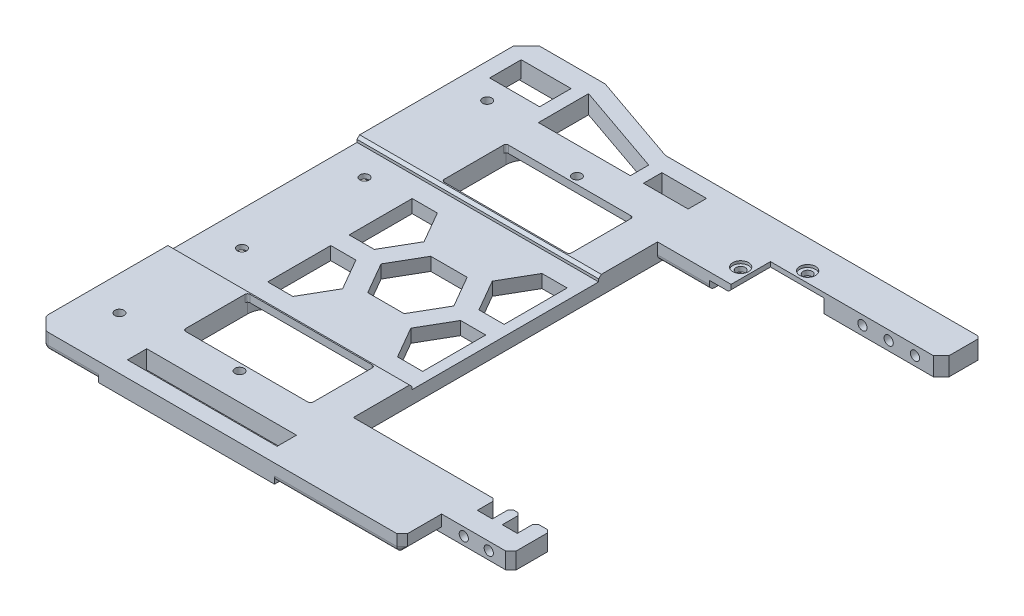
SolidWorks part; units mm, degrees
ref_plane "Front Plane" through (0, 0, 0) normal (0, 0, 1) x (1, 0, 0)
ref_plane "Top Plane" through (0, 0, 0) normal (0, 1, 0) x (1, 0, 0)
ref_plane "Right Plane" through (0, 0, 0) normal (1, 0, 0) x (0, 0, -1)
sketch "Sketch1" plane through (0, 0, 0) normal (0, 1, 0) x (1, 0, 0)
  line L0 (0, -49.205) -> (0, 49.205)
  line L1 (0, 0) -> (215.6, 0)
  line L2 (-50, -76.1325) -> (-50, 92.3676) construction
  line L3 (-25, 41.205) -> (25, 41.205)
  line L4 (-25, 41.205) -> (-25, 57.205)
  line L5 (-25, 57.205) -> (25, 57.205)
  line L6 (25, 41.205) -> (25, 57.205)
  line L7 (-25, 41.205) -> (25, 57.205) construction
  line L8 (-25, 57.205) -> (25, 41.205) construction
  line L9 (-25, -57.205) -> (25, -57.205)
  line L10 (-25, -57.205) -> (-25, -41.205)
  line L11 (-25, -41.205) -> (25, -41.205)
  line L12 (25, -57.205) -> (25, -41.205)
  line L13 (-25, -57.205) -> (25, -41.205) construction
  line L14 (-25, -41.205) -> (25, -57.205) construction
  line L15 (190.6, -8) -> (240.6, -8)
  line L16 (190.6, -8) -> (190.6, 8)
  line L17 (190.6, 8) -> (240.6, 8)
  line L18 (240.6, -8) -> (240.6, 8)
  line L19 (190.6, -8) -> (240.6, 8) construction
  line L20 (190.6, 8) -> (240.6, -8) construction
  line L21 (265.6, 85.2319) -> (265.6, -82.377) construction
  point P4 (0, 0)
  dimension "D1" = 50
  dimension "D2" = 16
  dimension "D3" = 98.41
  dimension "D4" = 215.6
  dimension "D5" = 50
  dimension "D6" = 50
sketch "Sketch2" plane through (0, 0, 0) normal (0, 1, 0) x (1, 0, 0)
  line L1 (10, 87.9) -> (130, 87.9)
  line L3 (37, -87.9) -> (-55, -87.9)
  line L4 (37, -87.9) -> (112, -87.9)
  line L5 (10, 87.9) -> (-25, 100)
  line L6 (-25, 100) -> (-55, 100)
  line L7 (-55, 100) -> (-55, -87.9)
  line L8 (37, -87.9) -> (37, 57.9) construction
  line L9 (37, 57.9) -> (130, 57.9)
  line L10 (130, 57.9) -> (130, 87.9)
  line L11 (10, 87.9) -> (10, -87.9) construction
  line L12 (0, 0) -> (215.6, 0) construction
  line L14 (0, -49.205) -> (0, 49.205) construction
  line L15 (112, -87.9) -> (112, -57.9)
  line L16 (112, -57.9) -> (37, -57.9)
  line L17 (37, -57.9) -> (37, 57.9)
  point P8 (10, 0)
  dimension "D1" = 100
  dimension "D2" = 92
  dimension "D3" = 30
  dimension "D4" = 87.9
  dimension "D5" = 30
  dimension "D6" = 55
  dimension "D7" = 130
  dimension "D8" = 65
  dimension "D9" = 30
  dimension "D10" = 75
extrude "Boss-Extrude1" add sketch "Sketch2" along normal blind 7
sketch "Sketch3" plane through (0, 0, 0) normal (0, -1, 0) x (1, 0, 0)
  line L0 (-25, -100) -> (-55, -100) construction
  line L1 (-55, 87.9) -> (-30, 87.9)
  line L2 (-55, 87.9) -> (-55, -92)
  line L3 (-55, -92) -> (-30, -92)
  line L4 (-30, 87.9) -> (-30, -92)
  dimension "D1" = 8
  dimension "D2" = 30
extrude "Cut-Extrude1" cut sketch "Sketch3" against normal blind 0.75
sketch "Sketch4" plane through (0, 0, 0) normal (0, -1, 0) x (1, 0, 0)
  line L0 (-25, 57.205) -> (25, 41.205) construction
  line L1 (24.25, -68.555) -> (-24.25, -68.555)
  line L2 (24.25, -68.555) -> (24.25, -29.855)
  line L3 (24.25, -29.855) -> (-24.25, -29.855)
  line L4 (-24.25, -68.555) -> (-24.25, -29.855)
  line L5 (24.25, -68.555) -> (-24.25, -29.855) construction
  line L6 (24.25, -29.855) -> (-24.25, -68.555) construction
  line L7 (24.25, 68.555) -> (-24.25, 68.555)
  line L8 (24.25, 68.555) -> (24.25, 29.855)
  line L9 (24.25, 29.855) -> (-24.25, 29.855)
  line L10 (-24.25, 68.555) -> (-24.25, 29.855)
  line L11 (24.25, 68.555) -> (-24.25, 29.855) construction
  line L12 (24.25, 29.855) -> (-24.25, 68.555) construction
  point P0 (0, -49.205)
  point P5 (0, 49.205)
  dimension "D1" = 48.5
  dimension "D2" = 38.7
extrude "Cut-Extrude2" cut sketch "Sketch4" against normal blind 4.2
sketch "Sketch5" plane through (0, 0, 0) normal (0, -1, 0) x (1, 0, 0)
  line L0 (-25, 57.205) -> (25, 41.205) construction
  line L1 (24.25, -36.955) -> (-24.25, -36.955)
  line L2 (24.25, -36.955) -> (24.25, -61.455)
  line L3 (24.25, -61.455) -> (-24.25, -61.455)
  line L4 (-24.25, -36.955) -> (-24.25, -61.455)
  line L5 (24.25, -36.955) -> (-24.25, -61.455) construction
  line L6 (24.25, -61.455) -> (-24.25, -36.955) construction
  line L7 (24.25, 61.455) -> (-24.25, 61.455)
  line L8 (24.25, 61.455) -> (24.25, 36.955)
  line L9 (24.25, 36.955) -> (-24.25, 36.955)
  line L10 (-24.25, 61.455) -> (-24.25, 36.955)
  line L11 (24.25, 61.455) -> (-24.25, 36.955) construction
  line L12 (24.25, 36.955) -> (-24.25, 61.455) construction
  line L13 (-24.25, 68.555) -> (-24.25, 29.855) construction
  line L14 (-24.25, -29.855) -> (-24.25, -68.555) construction
  point P0 (0, -49.205)
  point P5 (0, 49.205)
  dimension "D1" = 24.5
extrude "Cut-Extrude3" cut sketch "Sketch5" against normal through all
fillet "Fillet1" radius 7 8 edges at (-24.25, 2.1, 29.855) (-24.25, 2.1, 68.555) (24.25, 2.1, 29.855) (24.25, 2.1, 68.555) (24.25, 2.1, -29.855) (-24.25, 2.1, -29.855) (-24.25, 2.1, -68.555) (24.25, 2.1, -68.555)
fillet "Fillet2" radius 1 8 edges at (-24.25, 5.6, -36.955) (-24.25, 5.6, -61.455) (24.25, 5.6, -61.455) (24.25, 5.6, -36.955) (24.25, 5.6, 36.955) (24.25, 5.6, 61.455) (-24.25, 5.6, 36.955) (-24.25, 5.6, 61.455)
sketch "Sketch7" plane through (0, 0, 0) normal (0, -1, 0) x (1, 0, 0)
  line L1 (130, -57.9) -> (65, -57.9)
  line L2 (130, -57.9) -> (130, -72.9)
  line L3 (130, -72.9) -> (65, -72.9)
  line L4 (65, -57.9) -> (65, -72.9)
  line L5 (0, 0) -> (215.6, 0) construction
  line L6 (0, 49.205) -> (0, -49.205) construction
  dimension "D1" = 72.9
  dimension "D2" = 65
extrude "Cut-Extrude4" cut sketch "Sketch7" against normal through all
sketch "Sketch8" plane through (0, 7, 0) normal (0, 1, 0) x (1, 0, 0)
  line L0 (-55, 100) -> (-55, -87.9) construction
  line L1 (-55, -35.5) -> (37, -35.5)
  line L2 (-55, -35.5) -> (-55, 35.5)
  line L3 (-55, 35.5) -> (37, 35.5)
  line L4 (37, -35.5) -> (37, 35.5)
  line L6 (0, 0) -> (215.6, 0) construction
  line L7 (37, -57.9) -> (37, 57.9) construction
  point P8 (37, 0)
  dimension "D1" = 71
extrude "Cut-Extrude5" cut sketch "Sketch8" against normal blind 2
chamfer "Chamfer1" distance 1 angle 45 2 edges at (-9, 7, 35.5) (-9, 7, -35.5)
sketch "Sketch9" plane through (0, 0, 0) normal (0, -1, 0) x (1, 0, 0)
  line L0 (85.3, -57.9) -> (85.3, -80.9)
  line L2 (85.3, -80.9) -> (56.7, -80.9)
  line L4 (56.7, -80.9) -> (56.7, -57.9)
  line L6 (56.7, -57.9) -> (85.3, -57.9)
  line L8 (37, -57.9) -> (65, -57.9) construction
  line L9 (65, -57.9) -> (65, -72.9) construction
  line L10 (65, -72.9) -> (130, -72.9) construction
  dimension "D2" = 8.3
  dimension "D3" = 8
  dimension "D4" = 20.3
extrude "Cut-Extrude6" cut sketch "Sketch9" against normal blind 4.2
fillet "Fillet3" radius 4 1 edges at (56.7, 2.1, -80.9)
sketch "Sketch12" plane through (0, 0, 0) normal (0, -1, 0) x (1, 0, 0)
  line L0 (0, 0) -> (215.6, 0) construction
  line L1 (-10.3564, 0) -> (-3.4282, -12)
  line L2 (-3.4282, -12) -> (10.4282, -12)
  line L3 (10.4282, -12) -> (17.3564, 0)
  line L4 (17.3564, 0) -> (10.4282, 12)
  line L5 (10.4282, 12) -> (-3.4282, 12)
  line L6 (-3.4282, 12) -> (-10.3564, 0)
  line L7 (33, -27.5) -> (33, -3.5)
  line L8 (16.4904, -15.5) -> (23.4186, -27.5)
  line L9 (23.4186, -27.5) -> (33, -27.5)
  line L12 (33, -3.5) -> (23.4186, -3.5)
  line L13 (23.4186, -3.5) -> (16.4904, -15.5)
  line L14 (42.4333, -18.5655) -> (48.3862, -8.2549) [skipped]
  line L15 (37.1681, -3.3148) -> (30.9097, 7.5249) [skipped]
  line L16 (33, 3.5) -> (33, 27.5)
  line L17 (16.4904, 15.5) -> (23.4186, 3.5)
  line L18 (23.4186, 3.5) -> (33, 3.5)
  line L19 (33, 27.5) -> (23.4186, 27.5)
  line L20 (23.4186, 27.5) -> (16.4904, 15.5)
  line L21 (30.3468, -15.5) -> (30.3468, 15.5) construction
  line L22 (-26, -27.5) -> (-26, -3.5)
  line L24 (-26, -27.5) -> (-16.4186, -27.5)
  line L25 (-16.4186, -27.5) -> (-9.4904, -15.5)
  line L26 (-9.4904, -15.5) -> (-16.4186, -3.5)
  line L27 (-16.4186, -3.5) -> (-26, -3.5)
  line L30 (-26, 3.5) -> (-16.4186, 3.5)
  line L31 (-16.4186, 3.5) -> (-9.4904, 15.5)
  line L32 (-9.4904, 15.5) -> (-16.4186, 27.5)
  line L33 (-16.4186, 27.5) -> (-26, 27.5)
  line L35 (-38.0283, -14.0709) -> (-31.1001, -26.0709) [skipped]
  line L36 (-31.1001, -4.9291) -> (-38.0283, -16.9291) [skipped]
  line L37 (-38.0283, 16.9291) -> (-31.1001, 4.9291) [skipped]
  line L38 (-31.1001, 26.0709) -> (-38.0283, 14.0709) [skipped]
  line L39 (-26, 3.5) -> (-26, 27.5)
  line L41 (-30, -92) -> (-30, 87.9) construction
  line L42 (37, 35.5) -> (37, -35.5) construction
  circle A0 centre (3.5, 0) radius 12 construction
  circle A1 centre (30.3468, -15.5) radius 12 construction
  circle A2 centre (30.3468, 15.5) radius 12 construction
  circle A3 centre (-23.3468, -15.5) radius 12 construction
  circle A4 centre (-23.3468, 15.5) radius 12 construction
  dimension "D1" = 24
  dimension "D2" = 24
  dimension "D3" = 24
  dimension "D8" = 24
  dimension "D9" = 24
  dimension "D4" = 120
  dimension "D5" = 7
  dimension "D6" = 7
  dimension "D7" = 7
  dimension "D10" = 7
  dimension "D11" = 7
  dimension "D12" = 7
  dimension "D13" = 33.5
  dimension "D14" = 4
  dimension "D15" = 4
extrude "Cut-Extrude8" cut sketch "Sketch12" against normal blind 10
chamfer "Chamfer2" distance 3 angle 45 1 edges at (130, 3.5, -72.9)
sketch "Sketch13" plane through (0, 7, 0) normal (0, 1, 0) x (1, 0, 0)
  line L0 (0, 0) -> (215.6, 0) construction
  line L1 (112, -87.9) -> (85.6, -87.9)
  line L2 (112, -87.9) -> (112, -72.9)
  line L3 (112, -72.9) -> (85.6, -72.9)
  line L4 (85.6, -87.9) -> (85.6, -72.9)
  dimension "D1" = 72.9
  dimension "D2" = 26.4
extrude "Cut-Extrude9" cut sketch "Sketch13" against normal through all
sketch "Sketch14" plane through (0, 0, 0) normal (0, -1, 0) x (1, 0, 0)
  line L0 (-30, 87.9) -> (85.6, 87.9) construction
  line L1 (37, -72.9) -> (127, -72.9)
  line L2 (37, -72.9) -> (37, 87.9)
  line L3 (37, 87.9) -> (127, 87.9)
  line L4 (127, -72.9) -> (127, 87.9)
  line L6 (37, 57.9) -> (37, -57.9) construction
extrude "Cut-Extrude10" cut sketch "Sketch14" against normal blind 0.75
sketch "Sketch15" plane through (0, 0, -87.9) normal (0, 0, -1) x (-1, 0, 0)
  line L0 (-130, 3.5) -> (-90, 3.5) construction
  line L1 (-130, 7) -> (-130, 0) construction
  line L2 (-130, 0) -> (-10, 0) construction
  line L4 (-121.75, 3.5) -> (-121.75, 0) construction
  line L5 (-121.75, 0) -> (-118.25, 0) construction
  line L6 (-118.25, 3.5) -> (-118.25, 0) construction
  line L7 (-111.75, 3.5) -> (-111.75, 0) construction
  line L8 (-111.75, 0) -> (-108.25, 0) construction
  line L9 (-108.25, 3.5) -> (-108.25, 0) construction
  line L12 (-101.75, 3.5) -> (-101.75, 0) construction
  line L13 (-101.75, 0) -> (-98.25, 0) construction
  line L14 (-98.25, 3.5) -> (-98.25, 0) construction
  arc A0 (-121.75, 3.5) -> (-118.25, 3.5) centre (-120, 3.5) cw
  arc A1 (-111.75, 3.5) -> (-108.25, 3.5) centre (-110, 3.5) cw
  arc A2 (-101.75, 3.5) -> (-98.25, 3.5) centre (-100, 3.5) cw
  arc A3 (-121.75, 3.5) -> (-118.25, 3.5) centre (-120, 3.5) ccw
  arc A4 (-111.75, 3.5) -> (-108.25, 3.5) centre (-110, 3.5) ccw
  arc A5 (-101.75, 3.5) -> (-98.25, 3.5) centre (-100, 3.5) ccw
  point P6 (0, 0)
  dimension "D1" = 1.75
  dimension "D2" = 1.75
  dimension "D3" = 1.75
  dimension "D4" = 40
  dimension "D5" = 10
  dimension "D6" = 10
extrude "Cut-Extrude11" cut sketch "Sketch15" against normal up to next
sketch "Sketch16" plane through (0, -80.9, -87.9) normal (0, 0, 1) x (1, 0, 0)
  circle A0 centre (100, 84.4) radius 2.9
  circle A1 centre (110, 84.4) radius 2.9
  circle A2 centre (120, 84.4) radius 2.9
  dimension "D1" = 5.8
  dimension "D2" = 5.8
  dimension "D3" = 5.8
extrude "Cut-Extrude12" cut sketch "Sketch16" along normal blind 6
sketch "Sketch17" plane through (0, 0, 72.9) normal (0, 0, 1) x (1, 0, 0)
  line L0 (85.6, 3.875) -> (112, 3.875) construction
  line L1 (85.6, 0.75) -> (85.6, 7) construction
  line L2 (112, 0.75) -> (112, 7) construction
  line L3 (85.6, 0.75) -> (112, 0.75) construction
  line L5 (92.3, 3.875) -> (92.3, 0.75) construction
  line L6 (92.3, 0.75) -> (95.8, 0.75) construction
  line L7 (95.8, 3.875) -> (95.8, 0.75) construction
  line L8 (94.05, 3.875) -> (103.55, 3.875) construction
  line L10 (101.8, 3.875) -> (101.8, 0.75) construction
  line L11 (101.8, 0.75) -> (105.3, 0.75) construction
  line L12 (105.3, 3.875) -> (105.3, 0.75) construction
  arc A0 (92.3, 3.875) -> (95.8, 3.875) centre (94.05, 3.875) cw
  arc A1 (101.8, 3.875) -> (105.3, 3.875) centre (103.55, 3.875) cw
  arc A2 (92.3, 3.875) -> (95.8, 3.875) centre (94.05, 3.875) ccw
  arc A3 (101.8, 3.875) -> (105.3, 3.875) centre (103.55, 3.875) ccw
  point P6 (105.3, 3.875)
  point P19 (0, 0)
  point P21 (98.8, 3.875)
  dimension "D1" = 1.75
  dimension "D2" = 9.5
extrude "Cut-Extrude13" cut sketch "Sketch17" against normal up to next
sketch "Sketch18" plane through (0, 7, 0) normal (0, 1, 0) x (1, 0, 0)
  line L0 (112, -57.9) -> (37, -57.9) construction
  line L1 (106.4, -57.9) -> (100.7, -57.9)
  line L2 (106.4, -57.9) -> (106.4, -64.9)
  line L3 (106.4, -64.9) -> (100.7, -64.9)
  line L4 (100.7, -57.9) -> (100.7, -64.9)
  line L5 (95.8, -57.9) -> (92.3, -57.9) construction
  line L6 (96.9, -57.9) -> (91.2, -57.9)
  line L7 (96.9, -57.9) -> (96.9, -64.9)
  line L8 (96.9, -64.9) -> (91.2, -64.9)
  line L9 (91.2, -57.9) -> (91.2, -64.9)
  line L10 (105.3, -57.9) -> (101.8, -57.9) construction
  point P12 (94.05, -57.9)
  point P15 (103.55, -57.9)
  dimension "D1" = 5.7
  dimension "D2" = 7
extrude "Cut-Extrude14" cut sketch "Sketch18" against normal through all
chamfer "Chamfer3" distance 1 angle 45 2 edges at (75.15, 4.2, -72.9) (65, 4.2, -65.4)
sketch "Sketch19" plane through (0, 4.2, 0) normal (0, -1, 0) x (1, 0, 0)
  line L0 (75.15, -72.9) -> (75.15, -65.4) construction
  line L1 (65, -65.4) -> (56.7, -65.4) construction
  line L2 (75.15, -65.4) -> (65, -65.4) construction
  line L4 (56.7, -57.9) -> (56.7, -76.9) construction
  line L5 (75.15, -72.9) -> (75.15, -80.9) construction
  line L6 (65, -72.9) -> (85.3, -72.9) construction
  line L7 (60.7, -80.9) -> (85.3, -80.9) construction
  line L8 (65, -57.9) -> (65, -72.9) construction
  circle A0 centre (61.15, -65.4) radius 1.75
  circle A1 centre (75.15, -76.9) radius 1.75
  dimension "D1" = 3.5
  dimension "D2" = 3.5
  dimension "D3" = 11.5
  dimension "D4" = 14
extrude "Cut-Extrude15" cut sketch "Sketch19" against normal through all
fillet "Fillet4" radius 2 4 edges at (46.85, 0.75, -57.9) (61.3, 0.75, 87.9) (-42.5, 0.75, 87.9) (-55, 0.75, -2.05)
sketch "Sketch20" plane through (0, 7, 0) normal (0, 1, 0) x (1, 0, 0)
  circle A0 centre (61.15, 65.4) radius 3
  circle A1 centre (75.15, 76.9) radius 3
  dimension "D1" = 6
  dimension "D2" = 6
extrude "Cut-Extrude16" cut sketch "Sketch20" against normal blind 1
chamfer "Chamfer5" distance 1 angle 45 5 edges at (112, 3.875, 57.9) (106.4, 3.875, 57.9) (100.7, 3.875, 57.9) (96.9, 3.875, 57.9) (91.2, 3.875, 57.9)
chamfer "Chamfer6" distance 2 angle 45 4 edges at (85.6, 4.875, 87.9) (112, 3.875, 72.9) (85.6, 0.75, 79.4) (85.6, 1.3358, 87.3142)
sketch "Sketch21" plane through (0, 0, 0) normal (0, -1, 0) x (1, 0, 0)
  line L0 (-25, -93.6516) -> (10, -81.5516)
  line L1 (10, -81.5516) -> (10, -74.555)
  line L2 (10, -74.555) -> (-25, -74.555)
  line L3 (-25, -74.555) -> (-25, -93.6516)
  line L4 (10, -87.9) -> (-25, -100) construction
  line L5 (-17.25, -68.555) -> (17.25, -68.555) construction
  line L6 (-30, -92) -> (-30, 85.9) construction
  line L7 (-30, -92) -> (-30, 87.9) construction
  line L8 (32, 74.555) -> (-25, 74.555)
  line L9 (32, 74.555) -> (32, 81.9)
  line L10 (32, 81.9) -> (-25, 81.9)
  line L11 (-25, 74.555) -> (-25, 81.9)
  line L12 (-30, 87.9) -> (37, 87.9) construction
  line L13 (17.25, 68.555) -> (-17.25, 68.555) construction
  line L14 (37, 87.9) -> (37, -72.9) construction
  line L15 (32, -74.555) -> (32, 74.555) construction
  line L16 (15, -74.555) -> (32, -74.555)
  line L17 (15, -74.555) -> (15, -81.5516)
  line L18 (15, -81.5516) -> (32, -81.5516)
  line L19 (32, -74.555) -> (32, -81.5516)
  line L21 (10, -81.5516) -> (15, -81.5516) construction
  line L22 (10, -74.555) -> (15, -74.555) construction
  dimension "D1" = 6
  dimension "D2" = 6
  dimension "D3" = 5
  dimension "D4" = 5
  dimension "D5" = 6
  dimension "D6" = 6
  dimension "D7" = 5
  dimension "D8" = 5
extrude "Cut-Extrude17" cut sketch "Sketch21" against normal through all
sketch "Sketch23" plane through (0, 0.75, 0) normal (0, -1, 0) x (1, 0, 0)
  line L0 (-42, -92) -> (-42, 87.9) construction
  line L1 (-53, -92) -> (-30, -92) construction
  line L2 (-30, 87.9) -> (-55, 87.9) construction
  line L3 (-42, 67.95) -> (-42, -72.05) construction
  line L4 (-38.8246, -72.05) -> (-40.4123, -69.3)
  line L5 (-40.4123, -69.3) -> (-43.5877, -69.3)
  line L6 (-43.5877, -69.3) -> (-45.1754, -72.05) construction
  line L7 (-45.1754, -72.05) -> (-43.5877, -74.8) construction
  line L8 (-43.5877, -74.8) -> (-40.4123, -74.8)
  line L9 (-40.4123, -74.8) -> (-38.8246, -72.05)
  line L10 (-55, 87.9) -> (-55, -92) construction
  line L11 (-38.8246, 67.95) -> (-40.4123, 70.7)
  line L12 (-40.4123, 70.7) -> (-43.5877, 70.7)
  line L13 (-43.5877, 70.7) -> (-45.1754, 67.95) construction
  line L14 (-45.1754, 67.95) -> (-43.5877, 65.2) construction
  line L15 (-43.5877, 65.2) -> (-40.4123, 65.2)
  line L16 (-40.4123, 65.2) -> (-38.8246, 67.95)
  line L17 (-38.8246, -25.3833) -> (-40.4123, -22.6333)
  line L18 (-40.4123, -22.6333) -> (-43.5877, -22.6333)
  line L19 (-43.5877, -22.6333) -> (-45.1754, -25.3833) construction
  line L20 (-45.1754, -25.3833) -> (-43.5877, -28.1333) construction
  line L21 (-43.5877, -28.1333) -> (-40.4123, -28.1333)
  line L22 (-40.4123, -28.1333) -> (-38.8246, -25.3833)
  line L23 (-38.8246, 21.2833) -> (-40.4123, 24.0333)
  line L24 (-40.4123, 24.0333) -> (-43.5877, 24.0333)
  line L25 (-43.5877, 24.0333) -> (-45.1754, 21.2833) construction
  line L26 (-45.1754, 21.2833) -> (-43.5877, 18.5333) construction
  line L27 (-43.5877, 18.5333) -> (-40.4123, 18.5333)
  line L28 (-40.4123, 18.5333) -> (-38.8246, 21.2833)
  line L30 (-43.5877, 70.7) -> (-55, 70.7)
  line L32 (-43.5877, 65.2) -> (-55, 65.2)
  line L33 (-55, 70.7) -> (-55, 65.2)
  line L34 (-43.5877, 18.5333) -> (-55, 18.5333)
  line L36 (-43.5877, 24.0333) -> (-55, 24.0333)
  line L37 (-55, 18.5333) -> (-55, 24.0333)
  line L38 (-43.5877, -22.6333) -> (-55, -22.6333)
  line L40 (-43.5877, -28.1333) -> (-55, -28.1333)
  line L41 (-55, -22.6333) -> (-55, -28.1333)
  line L42 (-43.5877, -69.3) -> (-55, -69.3)
  line L44 (-43.5877, -74.8) -> (-55, -74.8)
  line L45 (-55, -69.3) -> (-55, -74.8)
  circle A0 centre (-42, -72.05) radius 2.75 construction
  circle A1 centre (-42, 67.95) radius 2.75 construction
  circle A2 centre (-42, -25.3833) radius 2.75 construction
  circle A3 centre (-42, 21.2833) radius 2.75 construction
  point P18 (-42, -2.05)
  dimension "D1" = 5.5
  dimension "D2" = 140
  dimension "D3" = 46.6667
  dimension "D4" = 46.6667
  dimension "D5" = 13
extrude "Cut-Extrude18" cut sketch "Sketch23" against normal blind 2.5
chamfer "Chamfer7" distance 1 angle 45 32 edges at (-46.7061, 0.75, 70.7) (-39.6184, 0.75, 69.325) (-46.7061, 0.75, 65.2) (-39.6184, 0.75, 66.575) (-46.7061, 0.75, 24.0333) (-39.6184, 0.75, 22.6583) (-46.7061, 0.75, 18.5333) (-39.6184, 0.75, 19.9083) (-46.7061, 0.75, -22.6333) (-39.6184, 0.75, -24.0083) (-39.6184, 0.75, -26.7583) (-46.7061, 0.75, -28.1333) (-46.7061, 0.75, -69.3) (-46.7061, 0.75, -74.8) (-39.6184, 0.75, -73.425) (-39.6184, 0.75, -70.675) (-55, 3, 70.7) (-55, 3, 65.2) (-54.4142, 1.3358, 70.7) (-54.4142, 1.3358, 65.2) (-55, 3, 24.0333) (-55, 3, 18.5333) (-54.4142, 1.3358, 24.0333) (-54.4142, 1.3358, 18.5333) (-55, 3, -22.6333) (-55, 3, -28.1333) (-54.4142, 1.3358, -22.6333) (-54.4142, 1.3358, -28.1333) (-55, 3, -69.3) (-55, 3, -74.8) (-54.4142, 1.3358, -69.3) (-54.4142, 1.3358, -74.8)
sketch "Sketch24" plane through (0, 0.75, 0) normal (0, -1, 0) x (1, 0, 0)
  circle A0 centre (-42, -72.05) radius 1.75
  circle A1 centre (-42, -25.3833) radius 1.75
  circle A2 centre (-42, 21.2833) radius 1.75
  circle A3 centre (-42, 67.95) radius 1.75
  dimension "D1" = 3.5
extrude "Cut-Extrude19" cut sketch "Sketch24" against normal through all
chamfer "Chamfer8" distance 1 angle 45 1 edges at (130, 3.5, -87.9)
sketch "Sketch25" plane through (0, 0, 0) normal (0, -1, 0) x (1, 0, 0)
  line L0 (-55, -75.8) -> (-55, -92) construction
  line L1 (-30, -92) -> (-49, -92)
  line L2 (-30, -92) -> (-30, -80)
  line L3 (-30, -80) -> (-49, -80)
  line L4 (-49, -92) -> (-49, -80)
  dimension "D1" = 12
  dimension "D2" = 6
extrude "Cut-Extrude20" cut sketch "Sketch25" against normal through all
chamfer "Chamfer9" distance 5 angle 45 2 edges at (-55, 3.5, -100) (-55, 4.875, 87.9)
sketch "Sketch26" plane through (0, 4.2, 0) normal (0, -1, 0) x (1, 0, 0)
  line L0 (0, -68.555) -> (0, -61.455) construction
  line L1 (-17.25, -68.555) -> (17.25, -68.555) construction
  line L2 (-23.25, -61.455) -> (23.25, -61.455) construction
  line L3 (0, 68.555) -> (0, 61.455) construction
  line L4 (17.25, 68.555) -> (-17.25, 68.555) construction
  line L5 (-23.25, 61.455) -> (23.25, 61.455) construction
  circle A0 centre (0, 64.205) radius 1.75
  circle A1 centre (0, -64.205) radius 1.75
  dimension "D1" = 3.5
  dimension "D2" = 3.5
  dimension "D3" = 15
  dimension "D4" = 15
extrude "Cut-Extrude21" cut sketch "Sketch26" against normal through all
fillet "Fillet5" radius 2 5 edges at (-50, 4.875, 87.9) (-50.5858, 1.3358, 87.3142) (-55, 4.875, 82.9) (-54.4142, 1.3358, 83.4858) (-52.5, 0.75, 85.4)
equation "\"D3@Sketch23\"=\"D2@Sketch23\"/3"
equation "\"D4@Sketch23\"=\"D2@Sketch23\"/3"
